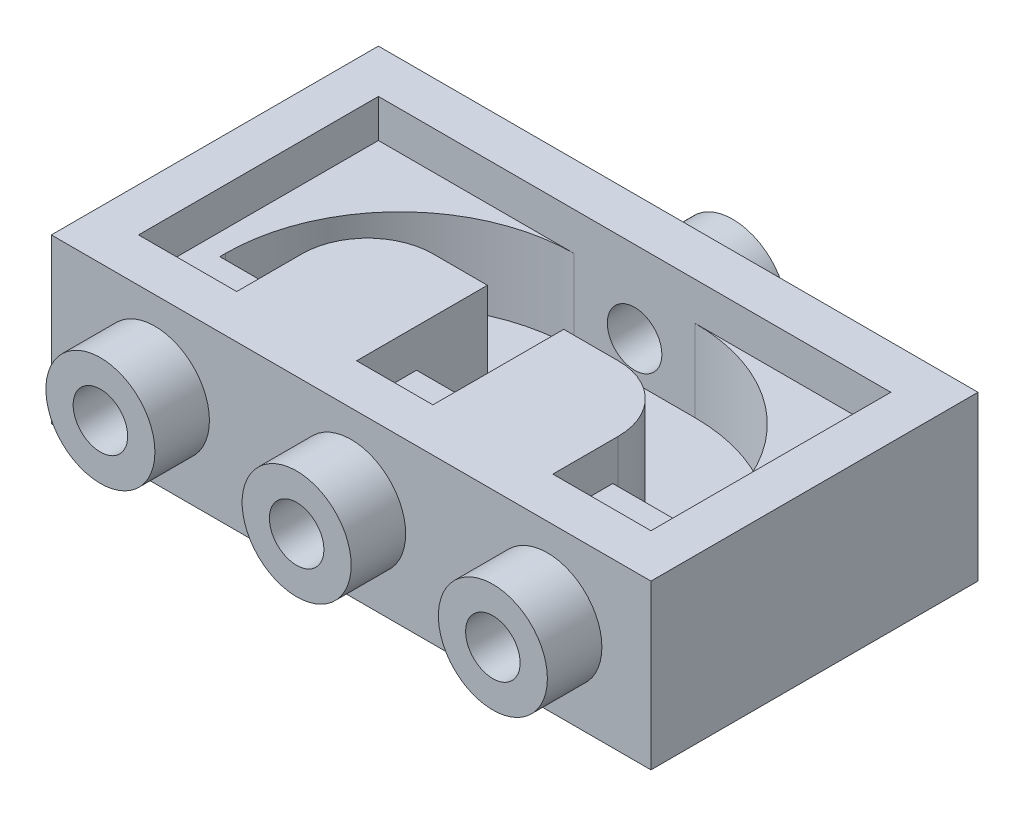
SolidWorks part; units mm, degrees
ref_plane "Front Plane" through (0, 0, 0) normal (0, 0, 1) x (1, 0, 0)
ref_plane "Top Plane" through (0, 0, 0) normal (0, 1, 0) x (1, 0, 0)
ref_plane "Right Plane" through (0, 0, 0) normal (1, 0, 0) x (0, 0, -1)
sketch "Sketch1" plane through (0, 0, 0) normal (0, 0, 1) x (1, 0, 0)
  line L1 (0, 0) -> (-110, 0)
  line L2 (0, 0) -> (0, 30)
  line L3 (0, 30) -> (-110, 30)
  line L4 (-110, 0) -> (-110, 30)
  dimension "D1" = 110
  dimension "30" = 30
extrude "Boss-Extrude1" add sketch "Sketch1" along normal blind 60
sketch "Sketch5" plane through (0, 0, 60) normal (0, 0, 1) x (1, 0, 0)
  line L0 (-110, 30) -> (-110, 0) construction
  line L1 (-110, 0) -> (0, 0) construction
  line L2 (0, 0) -> (0, 30) construction
  circle A0 centre (-91, 15) radius 10
  circle A1 centre (-55, 15) radius 10
  circle A2 centre (-19, 15) radius 10
  dimension "D1" = 19
  dimension "D2" = 15
  dimension "D3" = 20
  dimension "D5" = 19
  dimension "D6" = 15
  dimension "D4" = 3
extrude "Boss-Extrude3" add sketch "Sketch5" along normal blind 10
sketch "Sketch8" plane through (0, 0, 70) normal (0, 0, 1) x (1, 0, 0)
  line L1 (0, 0) -> (0, 30) construction
  line L2 (-110, 0) -> (0, 0) construction
  circle A0 centre (-91, 15) radius 5
  circle A1 centre (-91, 15) radius 10 construction
  circle A2 centre (-55, 15) radius 5
  circle A3 centre (-19, 15) radius 5
  dimension "D1" = 5
  dimension "D3" = 10
  dimension "D5" = 19
  dimension "D6" = 15
  dimension "D2" = 3
extrude "Cut-Extrude2" cut sketch "Sketch8" against normal blind 18
sketch "Sketch6" plane through (0, 0, 0) normal (0, 0, -1) x (-1, 0, 0)
  line L0 (0, 0) -> (0, 30) construction
  line L4 (110, 0) -> (0, 0) construction
  circle A0 centre (55, 15) radius 10
  dimension "D2" = 15
  dimension "D3" = 20
  dimension "D1" = 55
extrude "Boss-Extrude4" add sketch "Sketch6" along normal blind 10
sketch "Sketch7" plane through (0, 0, -10) normal (0, 0, -1) x (-1, 0, 0)
  line L0 (0, 30) -> (110, 30) construction
  line L1 (0, 0) -> (0, 30) construction
  circle A0 centre (55, 15) radius 5
  circle A1 centre (55, 15) radius 10 construction
  dimension "D1" = 5
  dimension "D2" = 15
  dimension "D3" = 55
extrude "Cut-Extrude3" cut sketch "Sketch7" against normal blind 18
shell "Shell6" thickness 8 removed face at (-60, 15, 8) removed face at (-14, 15, 52) removed face at (-86, 15, 52) removed face at (-50, 15, 52) removed face at (-55, 30, 30)
sketch "Sketch9" plane through (0, 8, 0) normal (0, 1, 0) x (1, 0, 0)
  line L0 (-102, -52) -> (-8, -52) construction
  line L1 (-84, -52) -> (-62, -52)
  line L2 (-84, -52) -> (-84, -28)
  line L3 (-84, -28) -> (-62, -28)
  line L4 (-62, -52) -> (-62, -28)
  line L5 (-102, -8) -> (-8, -8) construction
  line L6 (-102, -52) -> (-102, -8) construction
  dimension "D1" = 20
  dimension "D2" = 18
  dimension "D3" = 22
  dimension "D4" = 24
extrude "Boss-Extrude5" add sketch "Sketch9" along normal blind 22
sketch "Sketch10" plane through (0, 0, 60) normal (0, 0, 1) x (1, 0, 0)
  line L0 (-55, 30) -> (-55, 0) construction
  line L1 (0, 30) -> (-110, 30) construction
  line L2 (-110, 0) -> (0, 0) construction
ref_plane "Plane3" through (-55, 0, 0) normal (-1, 0, 0) x (0, -1, 0)
mirror "Mirror1" about plane through (-55, 0, 0) normal (-1, 0, 0) of "Boss-Extrude5"
fillet "Fillet2" radius 12 2 edges at (-26, 19, 28) (-84, 19, 28)
sketch "Sketch12" plane through (0, 0, 52) normal (0, 0, -1) x (-1, 0, 0)
  line L0 (55, 30) -> (55, 0) construction
  line L1 (48, 23) -> (62, 23)
  line L2 (48, 23) -> (48, 7)
  line L3 (48, 7) -> (62, 7)
  line L4 (62, 23) -> (62, 7)
  line L5 (48, 23) -> (62, 7) construction
  line L6 (48, 7) -> (62, 23) construction
  line L7 (62, 30) -> (62, 8) construction
  line L8 (48, 30) -> (62, 30) construction
  point P0 (55, 15)
  dimension "D1" = 16
  dimension "D2" = 7
extrude "Boss-Extrude8" add sketch "Sketch12" along normal blind 11
sketch "Sketch13" plane through (0, 0, 41) normal (0, 0, -1) x (-1, 0, 0)
  line L0 (55, 30) -> (55, 0) construction
  line L1 (62, 23) -> (48, 23) construction
  line L2 (62, 8) -> (62, 23) construction
  circle A0 centre (55, 15) radius 7
  dimension "D1" = 14
  dimension "D2" = 8
  dimension "D3" = 7
extrude "Cut-Extrude4" cut sketch "Sketch13" against normal blind 11 draft 10
sketch "Sketch14" plane through (0, 0, 52) normal (0, 0, -1) x (-1, 0, 0)
  line L0 (8, 8) -> (8, 30) construction
  line L1 (8, 23) -> (26, 23)
  line L2 (8, 23) -> (8, 8)
  line L3 (8, 8) -> (26, 8)
  line L4 (26, 23) -> (26, 8)
  dimension "D1" = 15
extrude "Boss-Extrude9" add sketch "Sketch14" along normal blind 11
sketch "Sketch16" plane through (0, 0, 41) normal (0, 0, -1) x (-1, 0, 0)
  line L0 (26, 23) -> (8, 23) construction
  circle A0 centre (19, 15) radius 7
  dimension "D1" = 14
  dimension "D2" = 8
extrude "Cut-Extrude5" cut sketch "Sketch16" against normal blind 11 draft 10
sketch "Sketch19" plane through (0, 0, 41) normal (0, 0, -1) x (-1, 0, 0)
  line L0 (8, 8) -> (19, 8) construction
  line L1 (8, 23) -> (11.9037, 23)
  line L2 (8, 23) -> (8, 8)
  line L3 (8, 8) -> (11.9037, 8)
  line L4 (11.9037, 23) -> (11.9037, 8)
extrude "Boss-Extrude11" add sketch "Sketch19" along normal blind 33.5
fillet "Fillet3" radius 32 1 edges at (-11.9037, 15.5, 8)
mirror "Mirror5" about plane through (-55, 0, 0) normal (-1, 0, 0) of "Cut-Extrude5", "Boss-Extrude11", "Boss-Extrude9", "Fillet3"
